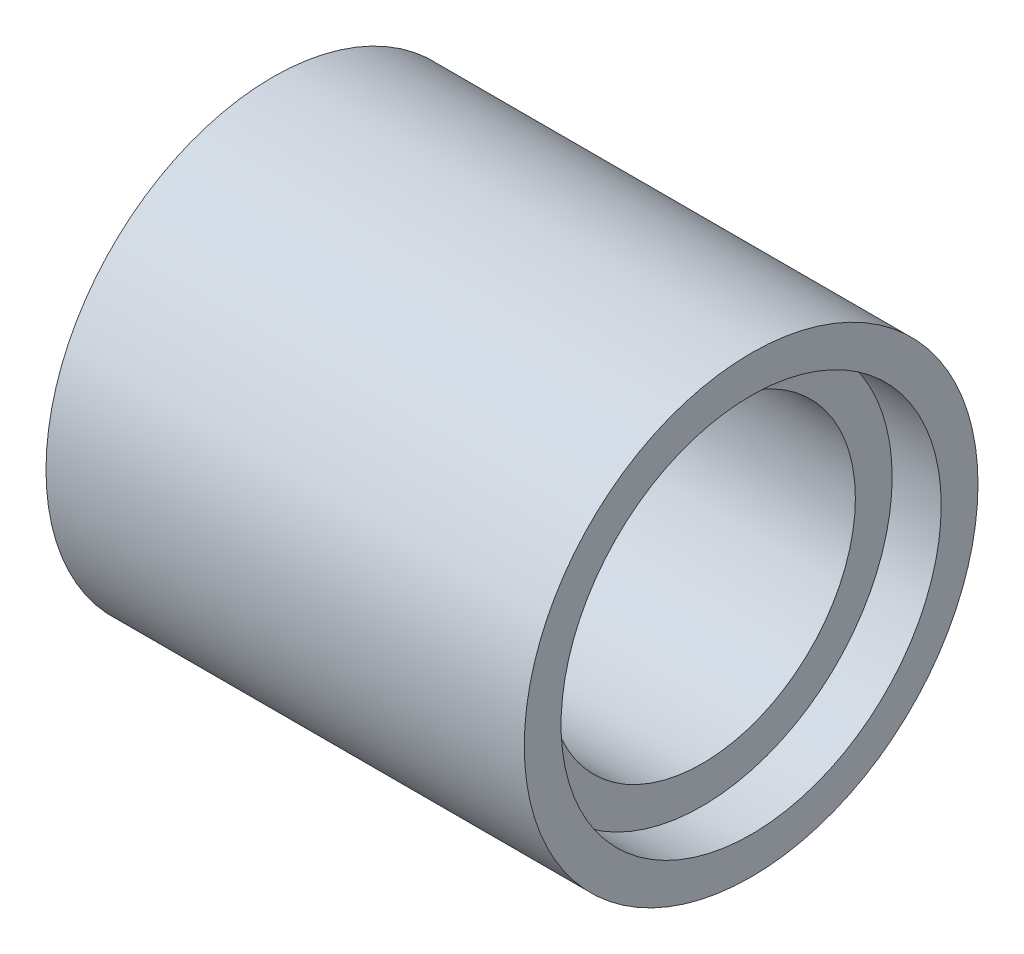
SolidWorks part; units mm, degrees
ref_plane "前视基准面" through (0, 0, 0) normal (0, 0, 1) x (1, 0, 0)
ref_plane "上视基准面" through (0, 0, 0) normal (0, 1, 0) x (1, 0, 0)
ref_plane "右视基准面" through (0, 0, 0) normal (1, 0, 0) x (0, 0, -1)
other "Configuration Table"
sketch "草图1" plane through (0, 0, 0) normal (1, 0, 0) x (0, 0, -1)
  circle A2 centre (0, 0) radius 3.7
  dimension "D1" = 7.4
extrude "凸台-拉伸1" add sketch "草图1" along normal mid plane 7.8
sketch "草图2" plane through (3.9, 0, 0) normal (1, 0, 0) x (0, 0, -1)
  circle A0 centre (0, 0) radius 2.5
  circle A1 centre (0, 0) radius 3.1
  dimension "D1" = 5
  dimension "D2" = 6.2
extrude "切除-拉伸1" cut sketch "草图2" against normal through all contours A0 region at (3.9, 0, 0)
extrude "切除-拉伸2" cut sketch "草图2<3>" against normal blind 0.8 contours A1 A0 region at (3.9, 0, 3.0123)
sketch "草图2<3>" plane through (3.9, 0, 0) normal (1, 0, 0) x (0, 0, -1) same geometry as "草图2"
mirror "镜向1" about plane through (0, 0, 0) normal (1, 0, 0) of "切除-拉伸2"
